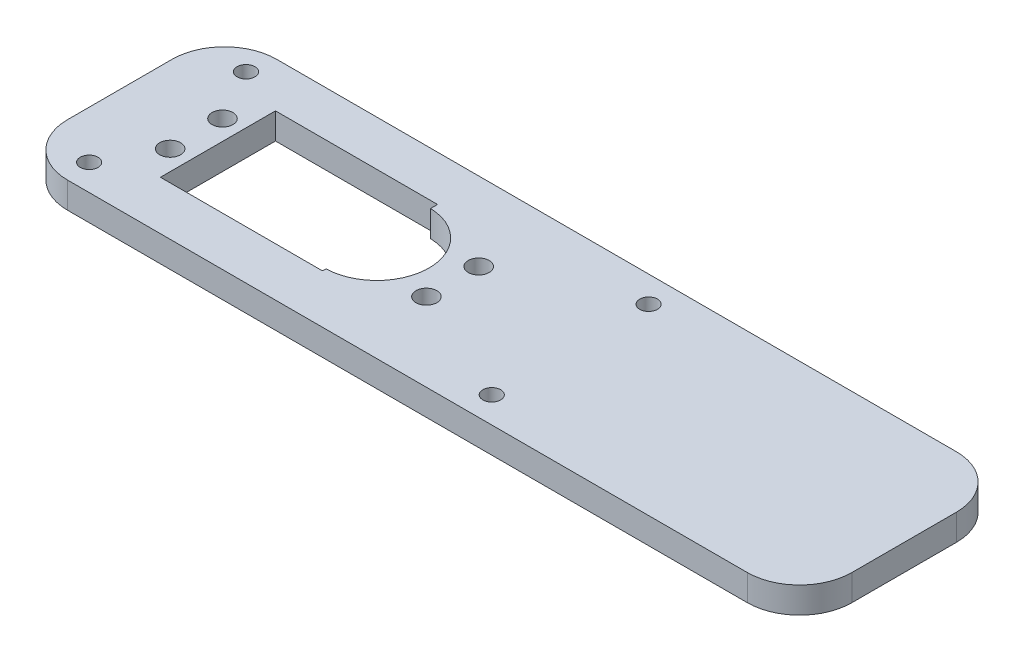
SolidWorks part; units mm, degrees
ref_plane "Front Plane" through (0, 0, 0) normal (0, 0, 1) x (1, 0, 0)
ref_plane "Top Plane" through (0, 0, 0) normal (0, 1, 0) x (1, 0, 0)
ref_plane "Right Plane" through (0, 0, 0) normal (1, 0, 0) x (0, 0, -1)
sketch "Sketch9" plane through (0, 0, 0) normal (0, 1, 0) x (1, 0, 0)
  line L5 (-49.1323, 20) -> (100.8677, 20)
  line L6 (-49.1323, 20) -> (-49.1323, -20)
  line L7 (-49.1323, -20) -> (100.8677, -20)
  line L8 (100.8677, 20) -> (100.8677, -20)
  line L9 (-49.1323, 20) -> (100.8677, -20) construction
  line L10 (-49.1323, -20) -> (100.8677, 20) construction
  point P0 (25.8677, 0)
  dimension "D1" = 40
  dimension "D2" = 150
extrude "Boss-Extrude5" add sketch "Sketch9" along normal blind 5 separate body
sketch "Sketch10" plane through (0, 5, 0) normal (0, 1, 0) x (1, 0, 0)
  line L4 (-30.7077, 11.3457) -> (-30.711, -10.6563)
  line L5 (-30.711, -10.6563) -> (0.2923, -10.661)
  line L6 (0.2923, -10.661) -> (0.2923, 11.339)
  line L7 (0.2923, 11.339) -> (-30.7077, 11.3457)
  circle A0 centre (14.5, 5) radius 2
  circle A1 centre (14.5, -5) radius 2
  circle A2 centre (-34.5, 5) radius 2
  circle A3 centre (-34.5, -5) radius 2
  circle A4 centre (0, 0) radius 10
  circle A5 centre (-13, 0) radius 8
  dimension "D1" = 16
  dimension "D2" = 10
  dimension "D3" = 10
  dimension "D6" = 20
  dimension "D7" = 2
  dimension "D9" = 14.5
  dimension "D10" = 34.5
  dimension "D11" = 13
  dimension "D4" = 31
  dimension "D5" = 22.002
  dimension "D8" = 14.5
  dimension "D12" = 5
  dimension "D13" = 11.339
  dimension "D14" = 30.7094
extrude "Cut-Extrude5" cut sketch "Sketch10" against normal through all contours A5 A4 L6 L7 L4 L5 | L6 A4 | A5 A4 L6 | A4 A5 | A4 A5 | A0 | A1 | A2 | A3 region at (-15.2078, 5, -10.9621) region at (4.4025, 5, 0) region at (-2.8641, 5, 0) region at (-7.5596, 5, 0) region at (-14.4547, 5, 0) region at (14.5, 5, -5) region at (14.5, 5, 5)
sketch "Sketch11" plane through (0, 5, 0) normal (0, 1, 0) x (1, 0, 0)
  circle A0 centre (-40, 15) radius 1.7
  circle A1 centre (37, 15) radius 1.7
  circle A2 centre (37, -15) radius 1.7
  circle A3 centre (-40, -15) radius 1.7
  dimension "D1" = 3.4
  dimension "D3" = 77
  dimension "D5" = 30
  dimension "D2" = 40
  dimension "D4" = 15
extrude "Cut-Extrude6" cut sketch "Sketch11" against normal through all
fillet "Fillet1" radius 10 4 edges at (100.8677, 2.5, 20) (-49.1323, 2.5, 20) (-49.1323, 2.5, -20) (100.8677, 2.5, -20)
sketch "Sketch12" plane through (0, 5, 0) normal (0, 1, 0) x (1, 0, 0)
  line L0 (-1.6323, 20) -> (-1.6323, -20)
  line L4 (-49.1323, 10) -> (-49.1323, -10) construction
  point P6 (0, 0)
  dimension "D1" = 47.5
